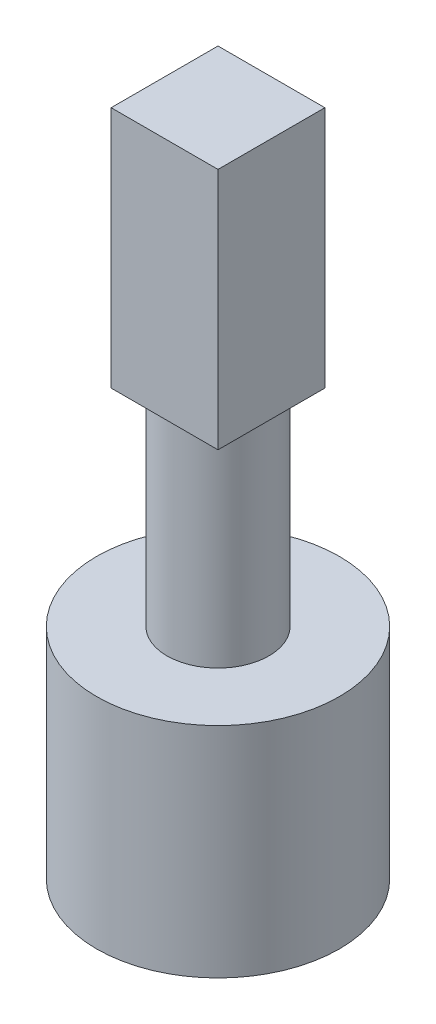
SolidWorks part; units mm, degrees
ref_plane "Front Plane" through (0, 0, 0) normal (0, 0, 1) x (1, 0, 0)
ref_plane "Top Plane" through (0, 0, 0) normal (0, 1, 0) x (1, 0, 0)
ref_plane "Right Plane" through (0, 0, 0) normal (1, 0, 0) x (0, 0, -1)
sketch "Sketch1" plane through (0, 0, 0) normal (0, 1, 0) x (1, 0, 0)
  line L1 (-3.3, 2.55) -> (3.3, 2.55)
  line L2 (-3.3, 2.55) -> (-3.3, -2.55)
  line L3 (-3.3, -2.55) -> (3.3, -2.55)
  line L4 (3.3, 2.55) -> (3.3, -2.55)
  line L5 (-3.3, 2.55) -> (3.3, -2.55) construction
  line L6 (-3.3, -2.55) -> (3.3, 2.55) construction
  circle A1 centre (0, 0) radius 5
  dimension "D2" = 10
  dimension "D1" = 5.1
  dimension "D3" = 6.6
extrude "Boss-Extrude1" add sketch "Sketch1" along normal blind 5
sketch "Sketch2" plane through (0, 5, 0) normal (0, 1, 0) x (1, 0, 0)
  circle A0 centre (0, 0) radius 5
  dimension "D1" = 10
extrude "Boss-Extrude2" add sketch "Sketch2" along normal blind 4
sketch "Sketch3" plane through (0, 9, 0) normal (0, 1, 0) x (1, 0, 0)
  circle A0 centre (0, 0) radius 2.1
  dimension "D1" = 4.2
extrude "Boss-Extrude3" add sketch "Sketch3" along normal blind 8.5
sketch "Sketch4" plane through (0, 17.5, 0) normal (0, 1, 0) x (1, 0, 0)
  line L1 (-2.2, -2.2) -> (2.2, -2.2)
  line L2 (-2.2, -2.2) -> (-2.2, 2.2)
  line L3 (-2.2, 2.2) -> (2.2, 2.2)
  line L4 (2.2, -2.2) -> (2.2, 2.2)
  line L5 (-2.2, -2.2) -> (2.2, 2.2) construction
  line L6 (-2.2, 2.2) -> (2.2, -2.2) construction
  point P0 (0, 0)
  dimension "D1" = 4.4
extrude "Boss-Extrude4" add sketch "Sketch4" along normal blind 10
